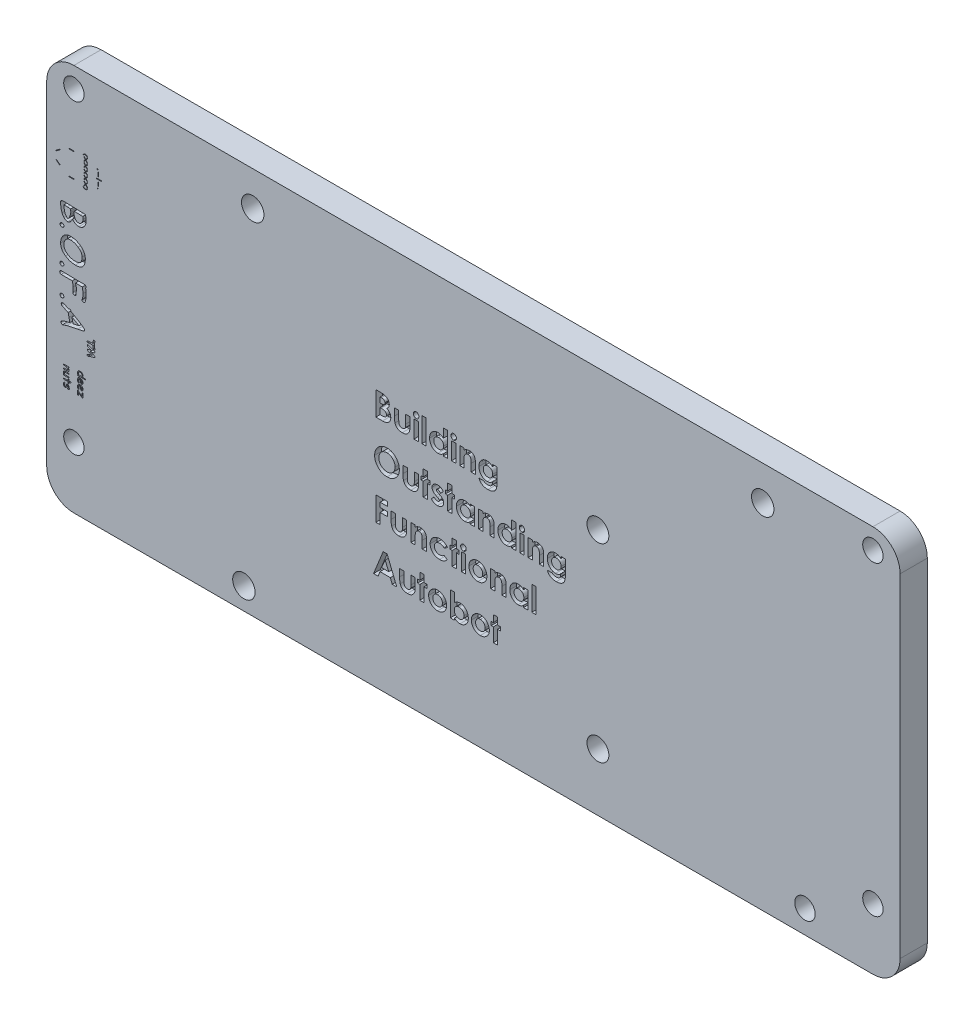
SolidWorks part; units mm, degrees
material "Acrylic (Medium-high impact)"
ref_plane "Front Plane" through (0, 0, 0) normal (0, 0, 1) x (1, 0, 0)
ref_plane "Top Plane" through (0, 0, 0) normal (0, 1, 0) x (1, 0, 0)
ref_plane "Right Plane" through (0, 0, 0) normal (1, 0, 0) x (0, 0, -1)
sketch "Sketch1" plane through (0, 0, 0) normal (0, 0, 1) x (1, 0, 0)
  line L1 (-44, 22.5848) -> (73.5, 22.5848)
  line L2 (-48, 18.5848) -> (-48, -30.4152)
  line L3 (-44, -34.4152) -> (73.5, -34.4152)
  line L4 (77.5, 18.5848) -> (77.5, -30.4152)
  circle A0 centre (-44, 19.5848) radius 1.5
  circle A1 centre (73.5, 19.5848) radius 1.5
  circle A2 centre (-44, -25.4152) radius 1.5
  circle A3 centre (73.5, -25.4152) radius 1.5
  circle A4 centre (-17.7, 17.5114) radius 1.65
  circle A5 centre (-19, -31.1886) radius 1.65
  circle A6 centre (57.3, 17.5114) radius 1.65
  arc A8 (-44, 22.5848) -> (-48, 18.5848) centre (-44, 18.5848) ccw
  arc A11 (-44, -34.4152) -> (-48, -30.4152) centre (-44, -30.4152) cw
  arc A12 (77.5, -30.4152) -> (73.5, -34.4152) centre (73.5, -30.4152) cw
  arc A13 (77.5, 18.5848) -> (73.5, 22.5848) centre (73.5, 18.5848) ccw
  circle A15 centre (63.5088, -31.0104) radius 1.5
  circle A16 centre (33.0607, -25.9322) radius 1.6081 construction
  circle A17 centre (33.0607, -25.9322) radius 1.6081
  circle A18 centre (33.0607, 1.9767) radius 1.6081 construction
  circle A19 centre (33.0607, 1.9767) radius 1.6081
  point P14 (-48, -34.4152)
  point P26 (-48, 22.5848)
  point P31 (0, 0)
  point P32 (52.1778, 17.5114)
  point P34 (0, 0)
  point P244 (77.5, 22.5848)
  point P320 (0, 0)
  point P545 (0, 0)
  dimension "D4" = 3
  dimension "D5" = 3
  dimension "D8" = 3
  dimension "D13" = 3
  dimension "D14" = 4
  dimension "D15" = 48.7
  dimension "D18" = 75
  dimension "D19" = 51.9266
  dimension "D20" = 3.3
  dimension "D21" = 3.3
  dimension "D22" = 3
  dimension "D23" = 3.3
  dimension "D24" = 4
  dimension "D9" = 4
  dimension "D10" = 4
  dimension "D1" = 125.5
  dimension "D3" = 117.5
  dimension "D6" = 4
  dimension "D7" = 4
  dimension "D11" = 3
  dimension "D12" = 45
  dimension "D16" = 48
  dimension "D17" = 5.0734
  dimension "D25" = 20.6081
  dimension "D34" = 3.2266
  dimension "D35" = 30.3
  dimension "D36" = 45
  dimension "D37" = 3
  dimension "D38" = 45
  dimension "D39" = 57
  dimension "D40" = 29
  dimension "D41" = 9
  dimension "D42" = 3.2266
  dimension "D43" = 3.2266
  dimension "D44" = 8.483
  dimension "D45" = 81.0607
  dimension "D46" = 3.4048
  dimension "D47" = 13.9912
  dimension "D48" = 5.0734
extrude "Boss-Extrude5" add sketch "Sketch1" along normal blind 4 contours L4 A13 L1 A8 L2 A11 L3 A12 A19 A17 A15 region at (14.6877, -5.9143, 0)
sketch "Sketch3" plane through (0, 0, 4) normal (0, 0, 1) x (1, 0, 0)
  text T0 "<b>Building</b>\r\n<b>Outstanding</b>\r\n<b>Functional</b>\r\n<b>Autobot</b>"
  point P1 (0, 0)
extrude "Cut-Extrude2" cut sketch "Sketch3" against normal blind 1
sketch "Sketch4" plane through (0, 0, 4) normal (0, 0, 1) x (1, 0, 0)
  line L0 (-45.8195, 9.429) -> (-45.8195, -16.0374) construction
  line L1 (-43.4432, -14.4628) -> (-43.4432, -20.5692) construction
  line L2 (-45.4918, -14.4628) -> (-45.4918, -20.7848) construction
  line L3 (-43.2912, -9.8716) -> (-43.2912, -14.4628) construction
  line L4 (-40.5327, 15.3498) -> (-40.5327, 4.382) construction
  text T0 "B.O.F.A" font "Comic Sans MS" height 3.5
  text T1 "deez" font "Comic Sans MS" height in points 4
  text T2 "nuts" font "Comic Sans MS" height in points 4
  text T3 "™" font "Comic Sans MS" height in points 8
  text T4 "   ,=|=.   \r\n   (XXXXX)   \r\n |         | \r\n    \\   /    " font "Nirmala UI" height in points 2
extrude "Cut-Extrude4" cut sketch "Sketch4" against normal blind 1
